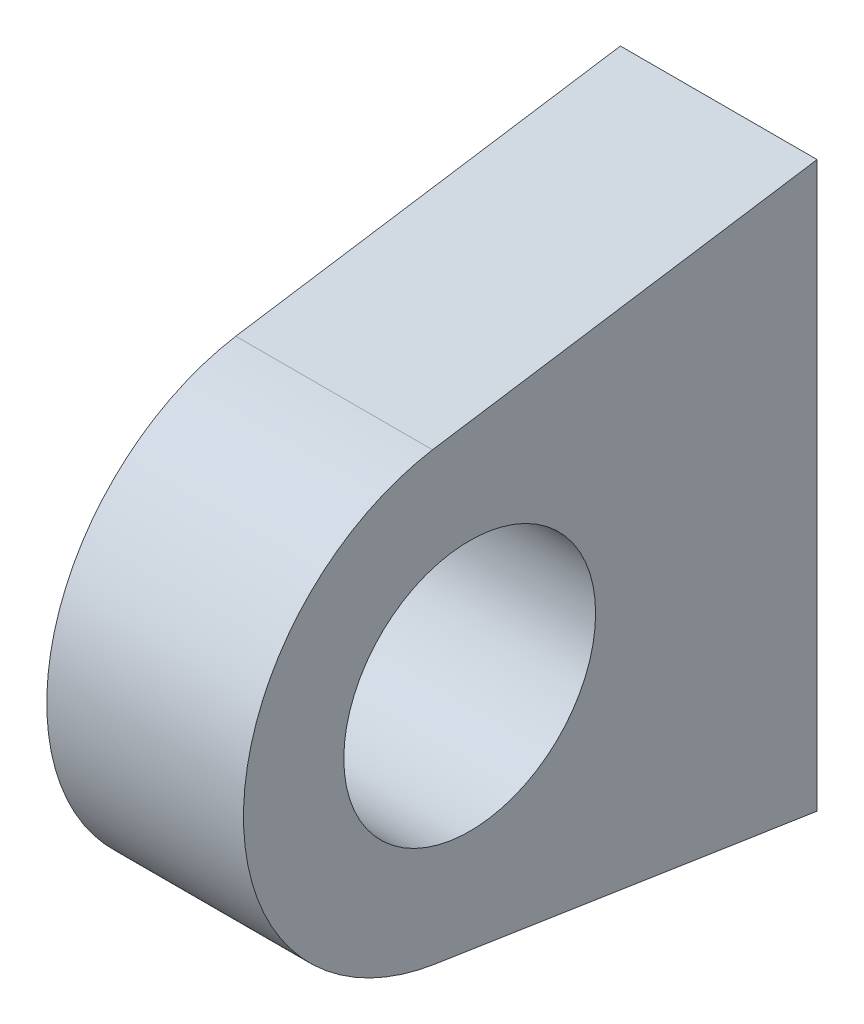
SolidWorks part; units mm, degrees
ref_plane "Płaszczyzna przednia" through (0, 0, 0) normal (0, 0, 1) x (1, 0, 0)
ref_plane "Płaszczyzna górna" through (0, 0, 0) normal (0, 1, 0) x (1, 0, 0)
ref_plane "Płaszczyzna prawa" through (0, 0, 0) normal (1, 0, 0) x (0, 0, -1)
sketch "Szkic19" plane through (91.7854, 0, 0) normal (1, 0, 0) x (0, 0, -1)
  line L1 (-28.446, 5.6717) -> (-18.6699, 7.1719)
  line L2 (-18.6699, 7.1719) -> (-18.6699, -7.1719)
  line L3 (-18.6699, -7.1719) -> (-28.3719, -5.6835)
  circle A1 centre (-27.5, 0) radius 3.2
  circle A2 centre (-27.5, 0) radius 5.75
  circle A3 centre (0, 0) radius 20 construction
  point P0 (0, 0)
  dimension "D2" = 11.5
extrude "Dodanie-wyciągnięcie4" add sketch "Szkic19" against normal blind 5 contours A2 L1 | A2 L1 A1 | A2 L3 region at (91.7854, 5.5222, 28.3474) region at (91.7854, -0.0002, 21.1744)
